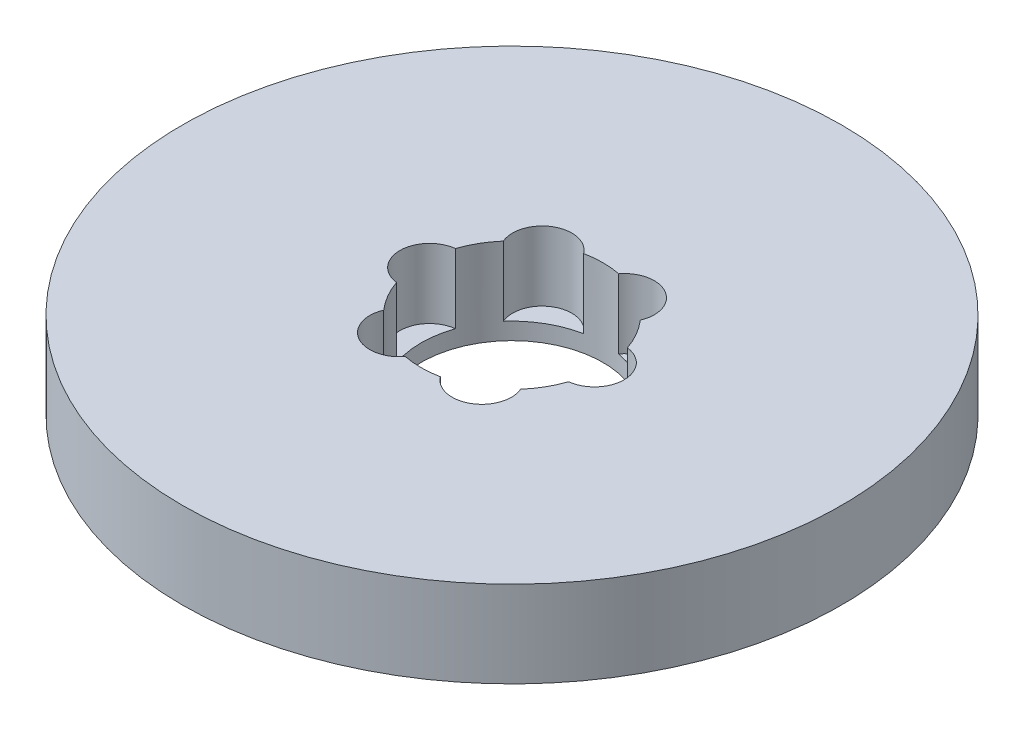
SolidWorks part; units mm, degrees
ref_plane "Front Plane" through (0, 0, 0) normal (0, 0, 1) x (1, 0, 0)
ref_plane "Top Plane" through (0, 0, 0) normal (0, 1, 0) x (1, 0, 0)
ref_plane "Right Plane" through (0, 0, 0) normal (1, 0, 0) x (0, 0, -1)
sketch "Sketch1" plane through (0, 0, 0) normal (0, 1, 0) x (1, 0, 0)
  circle A0 centre (0, 0) radius 72.5
  dimension "FLANGE_OD" = 145
extrude "Boss-Extrude1" add sketch "Sketch1" along normal blind 19
sketch "Sketch2" plane through (0, 0, 0) normal (0, 1, 0) x (1, 0, 0)
  circle A0 centre (0, 0) radius 20
  dimension "BORE_D" = 40
extrude "Cut-Extrude1" cut sketch "Sketch2" along normal through all
sketch "Sketch3" plane through (0, 19, 0) normal (0, 1, 0) x (1, 0, 0)
  circle A0 centre (0, 0) radius 18.1372 construction
  circle A1 centre (-18.1372, 0) radius 6.5172
  dimension "BOLT_D" = 13.0344
  dimension "BOLT_PCD" = 36.2744
extrude "Cut-Extrude2" cut sketch "Sketch3" against normal blind 15.276
pattern_circular "CirPattern1" count 6 over 360 about axis through (0, 0, 0) along (0, 1, 0) of "Cut-Extrude2"
